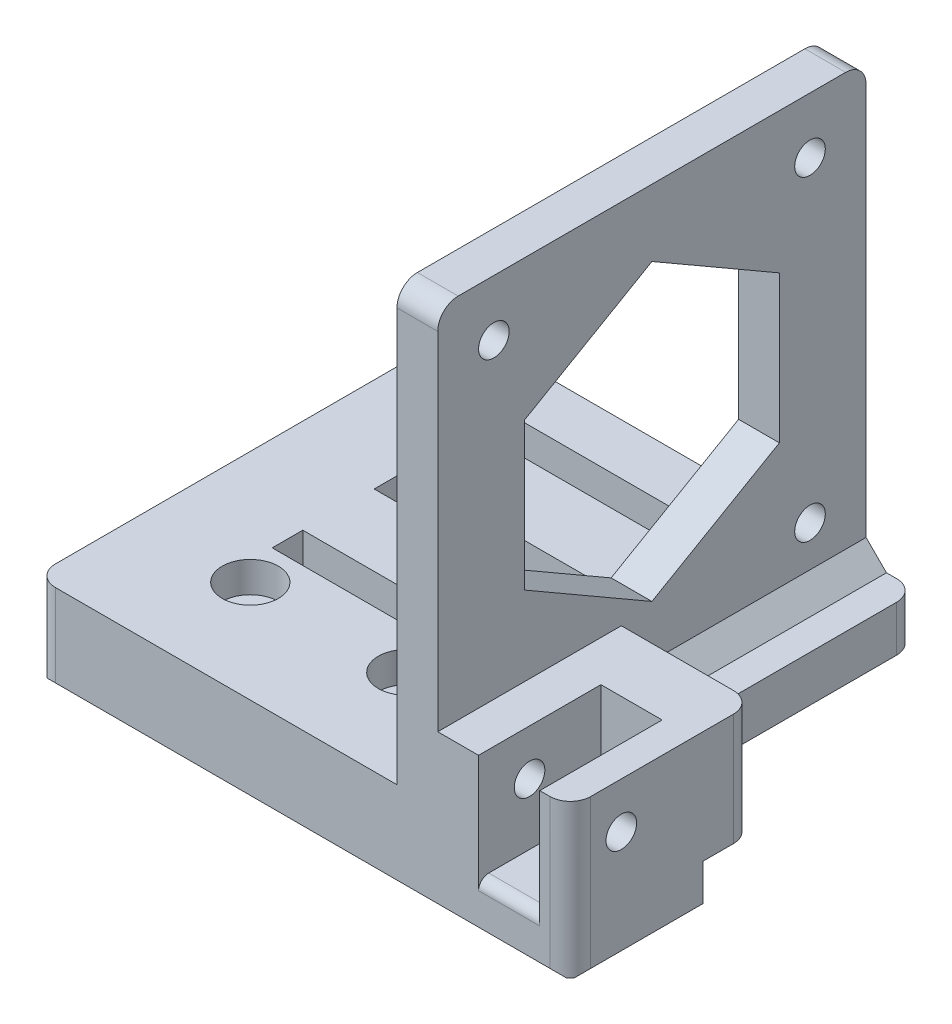
SolidWorks part; units mm, degrees
ref_plane "前视基准面" through (0, 0, 0) normal (0, 0, 1) x (1, 0, 0)
ref_plane "上视基准面" through (0, 0, 0) normal (0, 1, 0) x (1, 0, 0)
ref_plane "右视基准面" through (0, 0, 0) normal (1, 0, 0) x (0, 0, -1)
other "Configuration Table"
sketch "草图1" plane through (0, 0, 0) normal (0, 1, 0) x (1, 0, 0)
  line L1 (10, 0) -> (50, 0)
  line L2 (0, 0) -> (0, 42)
  line L3 (0, 42) -> (60, 42)
  line L4 (60, 0) -> (60, 42)
  line L6 (0, 0) -> (0, -20)
  line L7 (0, -20) -> (10, -20)
  line L8 (10, 0) -> (10, -20)
  line L14 (60, 0) -> (60, -20)
  line L15 (60, -20) -> (50, -20)
  line L16 (50, 0) -> (50, -20)
  point P11 (5, -20)
  dimension "D1" = 10
  dimension "D2" = 60
  dimension "D3" = 42
  dimension "D4" = 20
  dimension "D5" = 20
  dimension "D6" = 10
  dimension "D7" = 20
extrude "凸台-拉伸1" add sketch "草图1" along normal blind 5
sketch "草图3" plane through (0, 5, 0) normal (0, 1, 0) x (1, 0, 0)
  line L1 (56, 0) -> (60, 0)
  line L2 (56, 0) -> (56, 42)
  line L3 (56, 42) -> (60, 42)
  line L4 (60, 0) -> (60, 42)
  dimension "D1" = 4
extrude "凸台-拉伸2" add sketch "草图3" along normal blind 42
sketch "草图4" plane through (56, 0, 0) normal (-1, 0, 0) x (0, 0, 1)
  line L0 (-42, 47) -> (-36.5, 47) construction
  line L1 (-42, 47) -> (0, 47) construction
  line L2 (-36.5, 47) -> (-36.5, 41.5) construction
  line L3 (-36.5, 41.5) -> (-5.5, 41.5) construction
  line L4 (-5.5, 41.5) -> (-5.5, 10.5) construction
  line L5 (-5.5, 10.5) -> (-36.5, 10.5) construction
  circle A0 centre (-36.5, 41.5) radius 1.5
  circle A1 centre (-5.5, 41.5) radius 1.5
  circle A2 centre (-5.5, 10.5) radius 1.5
  circle A3 centre (-36.5, 10.5) radius 1.5
  dimension "D6" = 3
  dimension "D1" = 5.5
  dimension "D2" = 5.5
  dimension "D3" = 31
  dimension "D4" = 31
  dimension "D5" = 31
extrude "切除-拉伸1" cut sketch "草图4" against normal blind 42.5
sketch "草图5" plane through (56, 0, 0) normal (-1, 0, 0) x (0, 0, 1)
  line L0 (-42, 47) -> (0, 5) construction
  circle A0 centre (-21, 26) radius 12.5
  dimension "D1" = 25
extrude "切除-拉伸2" cut sketch "草图5" against normal blind 42.5
sketch "草图7" plane through (60, 0, 0) normal (1, 0, 0) x (0, 0, -1)
  line L1 (-20, 5) -> (0, 5)
  line L2 (-20, 5) -> (-20, 0)
  line L3 (-20, 0) -> (0, 0)
  line L4 (0, 5) -> (0, 0)
extrude "凸台-拉伸3" add sketch "草图7" along normal blind 5
sketch "草图8" plane through (0, 5, 0) normal (0, 1, 0) x (1, 0, 0)
  line L0 (50, -20) -> (65, -20) construction
  line L1 (65, 0) -> (56, 0)
  line L2 (65, 0) -> (65, -20)
  line L3 (65, -20) -> (56, -20)
  line L4 (56, 0) -> (56, -5)
  line L5 (56, -15) -> (56, -20)
  line L6 (56, -5) -> (61, -5)
  line L8 (56, -15) -> (61, -15)
  line L9 (61, -5) -> (61, -15)
  dimension "D1" = 9
  dimension "D2" = 5
  dimension "D3" = 5
  dimension "D4" = 5
extrude "凸台-拉伸5" add sketch "草图8" along normal up to surface (42 mm away) up to face at (58, 47, -21)
sketch "草图11" plane through (65, 0, 0) normal (1, 0, 0) x (0, 0, -1)
  line L4 (-20, 0) -> (0, 0)
  line L5 (-20, 5) -> (-20, 0)
  line L6 (0, 5) -> (-20, 5)
  line L7 (0, 0) -> (0, 5)
  line L8 (-20, 0) -> (0, 0)
  line L9 (-20, 5) -> (-20, 0)
  line L10 (0, 5) -> (-20, 5)
  line L11 (0, 0) -> (0, 5)
  dimension "D1" = 0
extrude "凸台-拉伸6" add sketch "草图11" along normal blind 18
sketch "草图12" plane through (0, 5, 0) normal (0, 1, 0) x (1, 0, 0)
  line L0 (83, -20) -> (65, -20) construction
  line L1 (83, 0) -> (79, 0)
  line L2 (83, 0) -> (83, -20)
  line L3 (83, -20) -> (79, -20)
  line L4 (79, 0) -> (79, -20)
  dimension "D1" = 4
extrude "凸台-拉伸7" add sketch "草图12" along normal up to surface (42 mm away) up to face at (59.6, 47, -0.4)
sketch "草图13" plane through (83, 0, 0) normal (1, 0, 0) x (0, 0, -1)
  line L0 (0, 47) -> (-20, 47) construction
  circle A0 centre (-10, 37) radius 1.6
  dimension "D1" = 10
  dimension "D2" = 3.2
extrude "切除-拉伸4" cut sketch "草图13" against normal up to surface (22 mm away) up to face at (61, 26, 10)
sketch "草图15" plane through (61, 0, 0) normal (-1, 0, 0) x (0, 0, 1)
  line L0 (15, 47) -> (15, 5) construction
  line L1 (5, 5) -> (15, 5)
  line L2 (5, 5) -> (5, 32)
  line L3 (5, 32) -> (15, 32)
  line L4 (15, 5) -> (15, 32)
  circle A0 centre (10, 37) radius 1.6 construction
  dimension "D1" = 5
extrude "切除-拉伸5" cut sketch "草图15" against normal up to surface (22 mm away)
sketch "草图16" plane through (0, 47, 0) normal (0, 1, 0) x (1, 0, 0)
  line L1 (61, -15) -> (56, -15)
  line L2 (61, -15) -> (61, -20)
  line L3 (61, -20) -> (56, -20)
  line L4 (56, -15) -> (56, -20)
extrude "切除-拉伸6" cut sketch "草图16" against normal up to surface (42 mm away) up to face at (54.3, 5, 5.8)
sketch "草图17" plane through (61, 0, 0) normal (-1, 0, 0) x (0, 0, 1)
  line L0 (5, 47) -> (5, 5) construction
  line L1 (15, 5) -> (5, 5)
  line L2 (15, 5) -> (15, 10)
  line L3 (15, 10) -> (5, 10)
  line L4 (5, 5) -> (5, 10)
  dimension "D1" = 5
extrude "凸台-拉伸8" add sketch "草图17" against normal up to surface (22 mm away)
sketch "草图19" plane through (0, 10, 0) normal (0, 1, 0) x (1, 0, 0)
  line L8 (79, -15) -> (83, -15)
  line L9 (83, -15) -> (83, -5)
  line L10 (83, -5) -> (79, -5)
  line L11 (79, -5) -> (65, -5)
  line L12 (65, -5) -> (61, -5)
  line L13 (61, -5) -> (61, -15)
  line L14 (61, -15) -> (65, -15)
  line L15 (65, -15) -> (79, -15)
  line L16 (79, -15) -> (83, -15)
  line L17 (83, -15) -> (83, -5)
  line L18 (83, -5) -> (79, -5)
  line L19 (79, -5) -> (65, -5)
  line L20 (65, -5) -> (61, -5)
  line L21 (61, -5) -> (61, -15)
  line L22 (61, -15) -> (65, -15)
  line L23 (65, -15) -> (79, -15)
  dimension "D1" = 0
extrude "切除-拉伸7" cut sketch "草图19" against normal up to surface (5 mm away) up to face at (35.4, 5, 0.6)
chamfer "倒角1" distance 7 angle 45 2 edges at (79, 5, 2.5) (65, 5, 2.5)
sketch "草图28" plane through (79, 0, 0) normal (-1, 0, 0) x (0, 0, 1)
  line L0 (15, 5) -> (15, 32) construction
  line L1 (15, 24) -> (20, 24)
  line L2 (15, 24) -> (15, 14)
  line L3 (15, 14) -> (20, 14)
  line L4 (20, 24) -> (20, 14)
  line L5 (20, 5) -> (20, 47) construction
  line L6 (15, 32) -> (5, 32) construction
  dimension "D1" = 8
  dimension "D2" = 10
extrude "凸台-拉伸10" add sketch "草图28" along normal up to next
sketch "草图29" plane through (0, 0, 0) normal (0, -1, 0) x (-1, 0, 0)
  line L0 (-10, -20) -> (-10, 0) construction
  line L1 (0, -20) -> (-10, -20)
  line L2 (0, -20) -> (0, -7)
  line L3 (0, -7) -> (-10, -7)
  line L4 (-10, -20) -> (-10, -7)
  line L5 (-83, -20) -> (-83, 0) construction
  line L6 (-50, -20) -> (-83, -20)
  line L7 (-50, -20) -> (-50, -7)
  line L8 (-50, -7) -> (-83, -7)
  line L9 (-83, -20) -> (-83, -7)
  line L10 (-10, 0) -> (-50, 0) construction
  dimension "D1" = 7
  dimension "D2" = 7
extrude "凸台-拉伸11" add sketch "草图29" along normal blind 3
sketch "草图30" plane through (10, 0, 0) normal (1, 0, 0) x (0, 0, -1)
  line L6 (-20, 5) -> (-20, -3)
  line L7 (-20, -3) -> (-7, -3)
  line L8 (-7, -3) -> (-7, 0)
  line L9 (-7, 0) -> (0, 0)
  line L10 (0, 0) -> (0, 5)
  line L11 (0, 5) -> (-20, 5)
  line L12 (-20, 5) -> (-20, -3)
  line L13 (-20, -3) -> (-7, -3)
  line L14 (-7, -3) -> (-7, 0)
  line L15 (-7, 0) -> (0, 0)
  line L16 (0, 0) -> (0, 5)
  line L17 (0, 5) -> (-20, 5)
  dimension "D1" = 0
extrude "凸台-拉伸12" add sketch "草图30" along normal blind 10
sketch "草图31" plane through (50, 0, 0) normal (-1, 0, 0) x (0, 0, 1)
  line L6 (0, 0) -> (7, 0)
  line L7 (7, 0) -> (7, -3)
  line L8 (7, -3) -> (20, -3)
  line L9 (20, -3) -> (20, 5)
  line L10 (20, 5) -> (0, 5)
  line L11 (0, 5) -> (0, 0)
  line L12 (0, 0) -> (7, 0)
  line L13 (7, 0) -> (7, -3)
  line L14 (7, -3) -> (20, -3)
  line L15 (20, -3) -> (20, 5)
  line L16 (20, 5) -> (0, 5)
  line L17 (0, 5) -> (0, 0)
  dimension "D1" = 0
extrude "凸台-拉伸13" add sketch "草图31" along normal blind 10
sketch "草图32" plane through (0, 0, 0) normal (-1, 0, 0) x (0, 0, 1)
  line L6 (-42, 0) -> (7, 0)
  line L7 (7, 0) -> (7, -3)
  line L8 (7, -3) -> (20, -3)
  line L9 (20, -3) -> (20, 5)
  line L10 (20, 5) -> (-42, 5)
  line L11 (-42, 5) -> (-42, 0)
  line L12 (-42, 0) -> (7, 0)
  line L13 (7, 0) -> (7, -3)
  line L14 (7, -3) -> (20, -3)
  line L15 (20, -3) -> (20, 5)
  line L16 (20, 5) -> (-42, 5)
  line L17 (-42, 5) -> (-42, 0)
  dimension "D1" = 0
extrude "切除-拉伸8" cut sketch "草图32" against normal blind 10
sketch "草图33" plane through (20, 0, 0) normal (1, 0, 0) x (0, 0, -1)
  line L6 (0, 5) -> (-20, 5)
  line L7 (-20, 5) -> (-20, -3)
  line L8 (-20, -3) -> (-7, -3)
  line L9 (-7, -3) -> (-7, 0)
  line L10 (-7, 0) -> (0, 0)
  line L11 (0, 0) -> (0, 5)
  line L12 (0, 5) -> (-20, 5)
  line L13 (-20, 5) -> (-20, -3)
  line L14 (-20, -3) -> (-7, -3)
  line L15 (-7, -3) -> (-7, 0)
  line L16 (-7, 0) -> (0, 0)
  line L17 (0, 0) -> (0, 5)
  dimension "D1" = 0
extrude "凸台-拉伸14" add sketch "草图33" along normal up to next
sketch "草图34" plane through (0, 5, 0) normal (0, 1, 0) x (1, 0, 0)
  line L0 (10, -20) -> (61, -20) construction
  circle A0 centre (19.2848, -10) radius 3
  circle A1 centre (51.1018, -10) radius 3
  dimension "D3" = 6
  dimension "D4" = 6
  dimension "D1" = 10
  dimension "D2" = 10
extrude "切除-拉伸9" cut sketch "草图34" against normal blind 3
sketch "草图35" plane through (0, 2, 0) normal (0, 1, 0) x (1, 0, 0)
  circle A0 centre (19.2848, -10) radius 1.5
  circle A1 centre (51.1018, -10) radius 1.5
  dimension "D1" = 3
  dimension "D2" = 3
extrude "切除-拉伸10" cut sketch "草图35" against normal through all
sketch "草图37" plane through (0, 5, 0) normal (0, 1, 0) x (1, 0, 0)
  line L0 (10, -20) -> (10, 42) construction
  line L1 (23, 31.8295) -> (48, 31.8295)
  line L2 (23, 31.8295) -> (23, 35.5641)
  line L3 (23, 35.5641) -> (48, 35.5641)
  line L4 (48, 31.8295) -> (48, 35.5641)
  line L5 (23, 21.8295) -> (48, 21.8295)
  line L6 (23, 25.5641) -> (48, 25.5641)
  line L7 (23, 21.8295) -> (23, 25.5641)
  line L8 (48, 21.8295) -> (48, 25.5641)
  line L9 (23, 11.8295) -> (48, 11.8295)
  line L10 (23, 15.5641) -> (48, 15.5641)
  line L11 (23, 11.8295) -> (23, 15.5641)
  line L12 (48, 11.8295) -> (48, 15.5641)
  line L13 (23, 5.5641) -> (48, 5.5641)
  line L14 (23, 1.8295) -> (48, 1.8295)
  line L15 (23, 1.8295) -> (23, 5.5641)
  line L16 (48, 1.8295) -> (48, 5.5641)
  dimension "D1" = 13
  dimension "D4" = 25
  dimension "D2" = 3
  dimension "D3" = 2
extrude "切除-拉伸11" cut sketch "草图37" against normal through all
sketch "草图38" plane through (61, 0, 0) normal (-1, 0, 0) x (0, 0, 1)
  line L6 (15, 32) -> (15, 5)
  line L7 (15, 5) -> (20, 5)
  line L8 (20, 5) -> (20, 47)
  line L9 (20, 47) -> (5, 47)
  line L10 (5, 47) -> (5, 32)
  line L11 (5, 32) -> (15, 32)
  line L12 (15, 32) -> (15, 5)
  line L13 (15, 5) -> (20, 5)
  line L14 (20, 5) -> (20, 47)
  line L15 (20, 47) -> (5, 47)
  line L16 (5, 47) -> (5, 32)
  line L17 (5, 32) -> (15, 32)
  dimension "D1" = 0
extrude "凸台-拉伸15" add sketch "草图38" along normal up to surface (5 mm away) up to face at (56, 26, -8.5)
sketch "草图39" plane through (65, 0, 0) normal (1, 0, 0) x (0, 0, -1)
  line L8 (-20, 47) -> (-20, 24)
  line L9 (-20, 24) -> (-15, 24)
  line L10 (-15, 24) -> (-15, 32)
  line L11 (-15, 32) -> (-5, 32)
  line L12 (-5, 32) -> (-5, 12)
  line L13 (-5, 12) -> (0, 12)
  line L14 (0, 12) -> (0, 47)
  line L15 (0, 47) -> (-20, 47)
  line L16 (-20, 47) -> (-20, 24)
  line L17 (-20, 24) -> (-15, 24)
  line L18 (-15, 24) -> (-15, 32)
  line L19 (-15, 32) -> (-5, 32)
  line L20 (-5, 32) -> (-5, 12)
  line L21 (-5, 12) -> (0, 12)
  line L22 (0, 12) -> (0, 47)
  line L23 (0, 47) -> (-20, 47)
  dimension "D1" = 0
extrude "切除-拉伸12" cut sketch "草图39" against normal up to surface (5 mm away) up to face at (60, 41.5, -35)
sketch "草图40" plane through (0, 47, 0) normal (0, 1, 0) x (1, 0, 0)
  line L1 (60, -5) -> (79, -5)
  line L2 (60, -5) -> (60, 0)
  line L3 (60, 0) -> (79, 0)
  line L4 (79, -5) -> (79, 0)
extrude "切除-拉伸13" cut sketch "草图40" against normal up to surface (42 mm away) up to face at (35.5, 5, -33.6968)
sketch "草图41" plane through (0, 47, 0) normal (0, 1, 0) x (1, 0, 0)
  line L1 (60, -20) -> (79, -20)
  line L2 (60, -20) -> (60, -15)
  line L3 (60, -15) -> (79, -15)
  line L4 (79, -20) -> (79, -15)
extrude "切除-拉伸14" cut sketch "草图41" against normal up to surface (42 mm away) up to face at (61, 5, 4.75)
sketch "草图42" plane through (0, 0, 20) normal (0, 0, 1) x (1, 0, 0)
  line L0 (69.5, 5) -> (60, 5)
  line L1 (79, 5) -> (60, 5) construction
  line L2 (60, 47) -> (60, 5) construction
  line L3 (60, 5) -> (60, 20)
  line L4 (79, 5) -> (79, 20)
  line L5 (79, 47) -> (79, 5) construction
  line L6 (79, 20) -> (60, 5)
  line L7 (60, 20) -> (79, 5)
  line M2 (79, 47) -> (79, 5)
  line M3 (79, 5) -> (60, 5)
  line M4 (60, 5) -> (60, 47)
  dimension "D1" = 15
extrude "凸台-拉伸16" add sketch "草图42" against normal up to surface (5 mm away) contours L7 L6 M4 | L7 L6 M3 | L6 L7 M2 up to face at (81, 18.5, 15)
sketch "草图43" plane through (0, 0, 0) normal (0, 0, -1) x (-1, 0, 0)
  line L0 (-79, 5) -> (-79, 20)
  line L1 (-79, 47) -> (-79, 5) construction
  line L2 (-79, 20) -> (-60, 5)
  line L3 (-60, 5) -> (-79, 5)
  line L4 (-60, 5) -> (-60, 20)
  line L5 (-60, 20) -> (-79, 5)
  line M3 (-60, 5) -> (-79, 5)
  line M4 (-79, 5) -> (-79, 47)
  dimension "D1" = 15
extrude "凸台-拉伸17" add sketch "草图43" against normal up to surface (5 mm away) contours L4 L5 L2 | L2 L5 M3 | L5 L2 M4 up to face at (81, 18.5, 5)
sketch "草图44" plane through (83, 0, 0) normal (1, 0, 0) x (0, 0, -1)
  line L6 (0, 0) -> (0, 47)
  line L7 (0, 47) -> (-20, 47)
  line L8 (-20, 47) -> (-20, -3)
  line L9 (-20, -3) -> (-7, -3)
  line L10 (-7, -3) -> (-7, 0)
  line L11 (-7, 0) -> (0, 0)
  line L12 (0, 0) -> (0, 47)
  line L13 (0, 47) -> (-20, 47)
  line L14 (-20, 47) -> (-20, -3)
  line L15 (-20, -3) -> (-7, -3)
  line L16 (-7, -3) -> (-7, 0)
  line L17 (-7, 0) -> (0, 0)
  circle A0 centre (-10, 37) radius 1.6 construction
  circle A1 centre (-10, 37) radius 1.6
  dimension "D1" = 0
extrude "切除-拉伸15" cut sketch "草图44" against normal through all contours A1
sketch "草图45" plane through (0, 0, 20) normal (0, 0, 1) x (1, 0, 0)
  line L11 (69.5, 12.5) -> (60, 20)
  line L12 (60, 20) -> (60, 47)
  line L13 (60, 47) -> (56, 47)
  line L14 (56, 47) -> (56, 5)
  line L15 (56, 5) -> (10, 5)
  line L16 (10, 5) -> (10, -3)
  line L17 (10, -3) -> (83, -3)
  line L18 (83, -3) -> (83, 47)
  line L19 (83, 47) -> (79, 47)
  line L20 (79, 47) -> (79, 20)
  line L21 (79, 20) -> (69.5, 12.5)
  line L22 (69.5, 12.5) -> (60, 20)
  line L23 (60, 20) -> (60, 47)
  line L24 (60, 47) -> (56, 47)
  line L25 (56, 47) -> (56, 5)
  line L26 (56, 5) -> (10, 5)
  line L27 (10, 5) -> (10, -3)
  line L28 (10, -3) -> (83, -3)
  line L29 (83, -3) -> (83, 47)
  line L30 (83, 47) -> (79, 47)
  line L31 (79, 47) -> (79, 20)
  line L32 (79, 20) -> (69.5, 12.5)
  dimension "D1" = 0
extrude "切除-拉伸16" cut sketch "草图45" against normal up to surface (20 mm away) up to face at (73.3571, 20.9286, 0)
sketch "草图46" plane through (0, 0, -1.8295) normal (0, 0, -1) x (-1, 0, 0)
  line L4 (-23, 0) -> (-23, 5)
  line L5 (-23, 5) -> (-48, 5)
  line L6 (-48, 5) -> (-48, 0)
  line L7 (-48, 0) -> (-23, 0)
  line L8 (-23, 0) -> (-23, 5)
  line L9 (-23, 5) -> (-48, 5)
  line L10 (-48, 5) -> (-48, 0)
  line L11 (-48, 0) -> (-23, 0)
  dimension "D1" = 0
extrude "凸台-拉伸18" add sketch "草图46" along normal up to next
sketch "草图48" plane through (0, 5, 0) normal (0, 1, 0) x (1, 0, 0)
  line L4 (10, 42) -> (10, 0)
  line L5 (10, 0) -> (56, 0)
  line L6 (56, 0) -> (56, 42)
  line L7 (56, 42) -> (10, 42)
  line L8 (10, 42) -> (10, 0)
  line L9 (10, 0) -> (56, 0)
  line L10 (56, 0) -> (56, 42)
  line L11 (56, 42) -> (10, 42)
  dimension "D1" = 0
extrude "切除-拉伸17" cut sketch "草图48" against normal blind 0.5
sketch "草图49" plane through (10, 0, 0) normal (-1, 0, 0) x (0, 0, 1)
  line L4 (0, 0) -> (0, 4.5)
  line L5 (0, 4.5) -> (-42, 4.5)
  line L6 (-42, 4.5) -> (-42, 0)
  line L7 (-42, 0) -> (0, 0)
  line L8 (0, 0) -> (0, 4.5)
  line L10 (-42, 4.5) -> (-42, 0)
  line L11 (-42, 0) -> (0, 0)
  line L13 (0, 4.5) -> (-42, 4.5)
  dimension "D1" = 0
extrude "切除-拉伸18" cut sketch "草图49" against normal blind 10.5
sketch "草图50" plane through (20.5, 0, 0) normal (-1, 0, 0) x (0, 0, 1)
  line L4 (-42, 0) -> (0, 0)
  line L5 (0, 0) -> (0, 4.5)
  line L6 (0, 4.5) -> (-42, 4.5)
  line L7 (-42, 4.5) -> (-42, 0)
  line L8 (-42, 0) -> (0, 0)
  line L9 (0, 0) -> (0, 4.5)
  line L11 (-42, 4.5) -> (-42, 0)
  line L13 (0, 4.5) -> (-42, 4.5)
  dimension "D1" = 0
extrude "凸台-拉伸19" add sketch "草图50" against normal offset from surface (49.5 mm away) 10 up to face at (60, 26, -8.5) offset beyond the face yes
sketch "草图51" plane through (0, 0, 0) normal (0, 0, 1) x (1, 0, 0)
  line L0 (60, 6.5) -> (62, 4.5)
  line L1 (60, 47) -> (60, 4.5) construction
  line L2 (70, 4.5) -> (60, 4.5) construction
  line L3 (62, 4.5) -> (60, 4.5)
  line L4 (60, 4.5) -> (60, 6.5)
  dimension "D1" = 2
  dimension "D2" = 2
sketch "草图52" plane through (0, 4.5, 0) normal (0, 1, 0) x (1, 0, 0)
  line L0 (29.7653, 24) -> (29.7653, 27)
  line L1 (29.7653, 34) -> (50.9151, 34)
  line L2 (29.7653, 34) -> (29.7653, 37)
  line L3 (29.7653, 37) -> (50.9151, 37)
  line L4 (50.9151, 34) -> (50.9151, 37)
  line L5 (29.7653, 24) -> (50.9151, 24)
  line L6 (50.9151, 24) -> (50.9151, 27)
  line L7 (29.7653, 27) -> (50.9151, 27)
  line L8 (29.7653, 14) -> (29.7653, 17)
  line L9 (29.7653, 14) -> (50.9151, 14)
  line L10 (50.9151, 14) -> (50.9151, 17)
  line L11 (29.7653, 17) -> (50.9151, 17)
  line L12 (56, 42) -> (20.5, 42) construction
  dimension "D2" = 3
  dimension "D3" = 5
  dimension "D1" = 3
extrude "切除-拉伸19" cut sketch "草图52" against normal through all
sketch "草图53" plane through (0, 0, 0) normal (0, -1, 0) x (-1, 0, 0)
  line L0 (-20.5, 42) -> (-20.5, 0) construction
  line L1 (-20.5, 13) -> (-70, 13)
  line L2 (-20.5, 13) -> (-20.5, 0)
  line L3 (-20.5, 0) -> (-70, 0)
  line L4 (-70, 13) -> (-70, 0)
  dimension "D1" = 13
extrude "凸台-拉伸21" add sketch "草图53" along normal blind 4
sketch "草图54" plane through (70, 0, 0) normal (1, 0, 0) x (0, 0, -1)
  line L6 (42, 0) -> (42, 4.5)
  line L7 (42, 4.5) -> (0, 4.5)
  line L8 (0, 4.5) -> (0, -4)
  line L9 (0, -4) -> (13, -4)
  line L10 (13, -4) -> (13, 0)
  line L11 (13, 0) -> (42, 0)
  line L12 (42, 0) -> (42, 4.5)
  line L13 (42, 4.5) -> (0, 4.5)
  line L14 (0, 4.5) -> (0, -4)
  line L15 (0, -4) -> (13, -4)
  line L16 (13, -4) -> (13, 0)
  line L17 (13, 0) -> (42, 0)
  dimension "D1" = 0
extrude "切除-拉伸20" cut sketch "草图54" against normal blind 5
sketch "草图55" plane through (0, 4.5, 0) normal (0, 1, 0) x (1, 0, 0)
  line L0 (20.5, 0) -> (56, 0) construction
  circle A0 centre (31.6171, 10) radius 2.75
  circle A1 centre (46.9167, 10) radius 2.75
  dimension "D1" = 5.5
  dimension "D2" = 5.5
  dimension "D3" = 10
  dimension "D4" = 10
extrude "切除-拉伸21" cut sketch "草图55" against normal blind 3
sketch "草图56" plane through (0, 1.5, 0) normal (0, 1, 0) x (1, 0, 0)
  circle A0 centre (31.6171, 10) radius 1.5
  circle A1 centre (46.9167, 10) radius 1.5
  dimension "D1" = 3
  dimension "D2" = 3
extrude "切除-拉伸22" cut sketch "草图56" against normal through all
sketch "草图57" plane through (65, 0, 0) normal (1, 0, 0) x (0, 0, -1)
  line L0 (42, 4.5) -> (0, 4.5) construction
  line L1 (0, -4) -> (13, -4)
  line L2 (0, -4) -> (0, 4.5)
  line L3 (0, 4.5) -> (13, 4.5)
  line L4 (13, -4) -> (13, 4.5)
extrude "凸台-拉伸22" add sketch "草图57" along normal blind 5
sketch "草图61" plane through (70, 0, 0) normal (1, 0, 0) x (0, 0, -1)
  line L4 (0, 4.5) -> (0, -4)
  line L5 (0, -4) -> (13, -4)
  line L6 (13, -4) -> (13, 4.5)
  line L7 (13, 4.5) -> (0, 4.5)
  line L8 (0, 4.5) -> (0, -4)
  line L9 (0, -4) -> (13, -4)
  line L10 (13, -4) -> (13, 4.5)
  line L11 (13, 4.5) -> (0, 4.5)
  dimension "D1" = 0
extrude "凸台-拉伸25" add sketch "草图61" along normal blind 3
sketch "草图64" plane through (0, 0, -13) normal (0, 0, -1) x (-1, 0, 0)
  line L0 (-65, 0) -> (-73, 0)
  line L6 (-20.5, 0) -> (-65, 0)
  line L7 (-65, 0) -> (-65, 4.5)
  line L8 (-65, 4.5) -> (-73, 4.5)
  line L9 (-73, 4.5) -> (-73, -4)
  line L10 (-73, -4) -> (-20.5, -4)
  line L11 (-20.5, -4) -> (-20.5, 0)
  line L12 (-20.5, 0) -> (-65, 0)
  line L13 (-65, 0) -> (-65, 4.5)
  line L14 (-65, 4.5) -> (-73, 4.5)
  line L15 (-73, 4.5) -> (-73, -4)
  line L16 (-73, -4) -> (-20.5, -4)
  line L17 (-20.5, -4) -> (-20.5, 0)
  line M8 (-65, 0) -> (-65, 4.5)
  line M9 (-65, 4.5) -> (-73, 4.5)
  line M10 (-73, 4.5) -> (-73, -4)
  dimension "D1" = 0
extrude "凸台-拉伸26" add sketch "草图64" along normal blind 5 contours L0 M8 M9 M10
sketch "草图65" plane through (0, 4.5, 0) normal (0, 1, 0) x (1, 0, 0)
  line L0 (65, 18) -> (60, 18)
  line L6 (60, 0) -> (73, 0)
  line L7 (73, 0) -> (73, 18)
  line L8 (73, 18) -> (65, 18)
  line L9 (65, 18) -> (65, 42)
  line L10 (65, 42) -> (60, 42)
  line L11 (60, 42) -> (60, 0)
  line L12 (60, 0) -> (73, 0)
  line L13 (73, 0) -> (73, 18)
  line L14 (73, 18) -> (65, 18)
  line L15 (65, 18) -> (65, 42)
  line L16 (65, 42) -> (60, 42)
  line L17 (60, 42) -> (60, 0)
  line M7 (60, 0) -> (73, 0)
  line M8 (73, 0) -> (73, 18)
  line M9 (73, 18) -> (65, 18)
  line M12 (60, 42) -> (60, 0)
  dimension "D1" = 0
extrude "凸台-拉伸27" add sketch "草图65" along normal blind 5 contours L0 M9 M12 M7 M8
sketch "草图62" plane through (0, 4.5, 0) normal (0, 1, 0) x (1, 0, 0)
  line L0 (73, 13) -> (73, 0) construction
  line L1 (64, 0) -> (70, 0)
  line L2 (64, 0) -> (64, 12)
  line L3 (64, 12) -> (70, 12)
  line L4 (70, 0) -> (70, 12)
  dimension "D1" = 3
  dimension "D2" = 6
  dimension "D3" = 12
extrude "切除-拉伸23" cut sketch "草图62" against normal blind 4 and the other way through all
fillet "圆角2" radius 1 1 edges at (67, 0.5, 0)
sketch "草图63" plane through (73, 0, 0) normal (1, 0, 0) x (0, 0, -1)
  line L0 (0, 9.5) -> (0, -4) construction
  line L2 (0, 9.5) -> (18, 9.5) construction
  circle A0 centre (5, 6.5) radius 1.5
  dimension "D1" = 3
  dimension "D3" = 3
  dimension "D2" = 5
extrude "切除-拉伸24" cut sketch "草图63" against normal blind 12
sketch "草图66" plane through (56, 0, 0) normal (-1, 0, 0) x (0, 0, 1)
  circle A0 centre (-5.5, 10.5) radius 1.5 construction
  circle A1 centre (-5.5, 10.5) radius 1.5
extrude "凸台-拉伸28" add sketch "草图66" against normal up to surface (4 mm away) up to face at (60, 26, -8.5)
chamfer "倒角2" distance 0.4 angle 45 6 edges at (20.5, -4, -6.5) (46.75, -4, 0) (73, -4, -6.5) (46.75, -4, -13) (46.9167, -4, -8.5) (31.6171, -4, -8.5)
fillet "圆角3" radius 2 4 edges at (20.5, 2.25, -42) (58, 47, 0) (58, 47, -42) (65, 2.25, -42)
sketch "草图67" plane through (0, 0, -42) normal (0, 0, -1) x (-1, 0, 0)
  line L0 (-60, 6.5) -> (-60, 4.5)
  line L1 (-60, 4.5) -> (-62, 4.5)
  line L2 (-62, 4.5) -> (-60, 6.5)
extrude "凸台-拉伸29" add sketch "草图67" against normal up to surface (24 mm away) up to face at (66, 4.6667, -18)
fillet "圆角4" radius 2 3 edges at (73, 4.75, -18) (73, 2.95, 0) (20.5, 0.45, 0)
sketch "草图68" plane through (60, 0, 0) normal (1, 0, 0) x (0, 0, -1)
  line L1 (21, 40.4338) -> (8.5, 33.2169)
  line L2 (8.5, 33.2169) -> (8.5, 18.7831)
  line L3 (8.5, 18.7831) -> (21, 11.5662)
  line L4 (21, 11.5662) -> (33.5, 18.7831)
  line L5 (33.5, 18.7831) -> (33.5, 33.2169)
  line L6 (33.5, 33.2169) -> (21, 40.4338)
  circle A0 centre (21, 26) radius 12.5 construction
  point P1 (27.25, 36.8253)
  dimension "D1" = 12.5
extrude "切除-拉伸25" cut sketch "草图68" against normal up to next
sketch "草图69" plane through (0, 9.5, 0) normal (0, 1, 0) x (1, 0, 0)
  line L8 (73, 2) -> (73, 16)
  line L9 (71, 18) -> (60, 18)
  line L10 (60, 18) -> (60, 0)
  line L11 (60, 0) -> (64, 0)
  line L12 (64, 0) -> (64, 12)
  line L13 (64, 12) -> (70, 12)
  line L14 (70, 12) -> (70, 0)
  line L15 (70, 0) -> (71, 0)
  line L16 (73, 2) -> (73, 16)
  line L17 (71, 18) -> (60, 18)
  line L18 (60, 18) -> (60, 0)
  line L19 (60, 0) -> (64, 0)
  line L20 (64, 0) -> (64, 12)
  line L21 (64, 12) -> (70, 12)
  line L22 (70, 12) -> (70, 0)
  line L23 (70, 0) -> (71, 0)
  arc A2 (73, 16) -> (71, 18) centre (71, 16) ccw
  arc A3 (71, 0) -> (73, 2) centre (71, 2) ccw
  arc A4 (73, 16) -> (71, 18) centre (71, 16) ccw
  arc A5 (71, 0) -> (73, 2) centre (71, 2) ccw
  dimension "D1" = 0
extrude "凸台-拉伸30" add sketch "草图69" along normal blind 1.5
